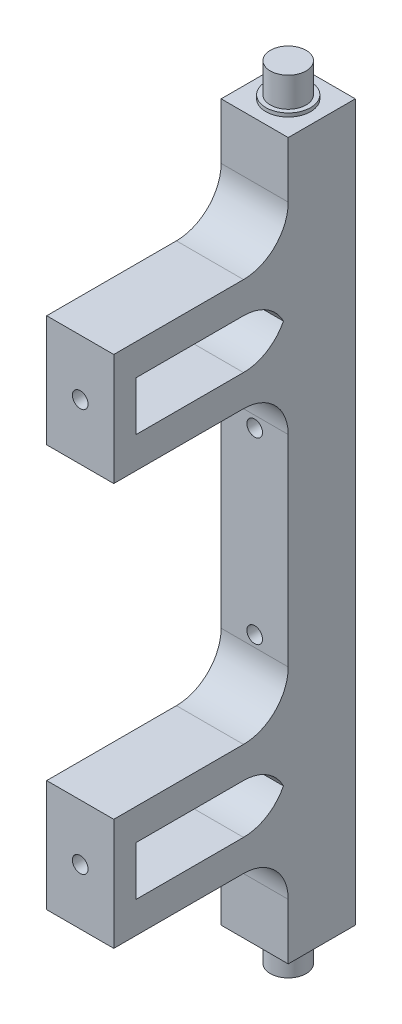
SolidWorks part; units mm, degrees
ref_plane "Plan de face" through (0, 0, 0) normal (1, 0, 0) x (0, 1, 0)
ref_plane "Plan de dessus" through (0, 0, 0) normal (0, 0, 1) x (0, 1, 0)
ref_plane "Plan de droite" through (0, 0, 0) normal (0, 1, 0) x (-1, 0, 0)
sketch "Esquisse1" plane through (0, 0, 0) normal (0, 0, 1) x (0, 1, 0)
  line L0 (0, 0) -> (-102.3211, 0) construction
  line L1 (-57.5, 7.5) -> (-32.5, 7.5)
  line L2 (-57.5, 7.5) -> (-57.5, -7.5)
  line L3 (-57.5, -7.5) -> (-32.5, -7.5)
  line L4 (-32.5, 7.5) -> (-32.5, -7.5)
  line L5 (-57.5, 7.5) -> (-32.5, -7.5) construction
  line L6 (-57.5, -7.5) -> (-32.5, 7.5) construction
  line L7 (0, 0) -> (0, -24.159) construction
  line L8 (57.5, -7.5) -> (32.5, -7.5)
  line L9 (32.5, 7.5) -> (32.5, -7.5)
  line L10 (57.5, 7.5) -> (32.5, 7.5)
  line L11 (57.5, 7.5) -> (57.5, -7.5)
  point P0 (-45, 0)
  dimension "D1" = 45
  dimension "D2" = 25
  dimension "D3" = 15
extrude "Boss.-Extru.1" add sketch "Esquisse1" along normal blind 39
sketch "Esquisse3" plane through (0, 0, 0) normal (0, 0, 1) x (0, 1, 0)
  line L1 (-80, -7.5) -> (80, -7.5)
  line L2 (-80, -7.5) -> (-80, 7.5)
  line L3 (-80, 7.5) -> (80, 7.5)
  line L4 (80, -7.5) -> (80, 7.5)
  line L5 (-80, -7.5) -> (80, 7.5) construction
  line L6 (-80, 7.5) -> (80, -7.5) construction
  point P0 (0, 0)
  dimension "D1" = 160
  dimension "D2" = 15
extrude "Boss.-Extru.2" add sketch "Esquisse3" against normal blind 15
sketch "Esquisse4" plane through (0, -80, 0) normal (0, -1, 0) x (-1, 0, 0)
  line L0 (-7.5, 0) -> (7.5, 15) construction
  line L1 (7.5, 15) -> (7.5, 0) construction
  line L2 (7.5, 0) -> (-7.5, 15) construction
  circle A0 centre (0, 7.5) radius 4
  circle A1 centre (0, 7.5) radius 5
  dimension "D1" = 10
extrude "Boss.-Extru.5" add sketch "Esquisse4" along normal blind 0.8 contours A0 | A1 region at (0, -80, -7.5)
extrude "Boss.-Extru.6" add sketch "Esquisse4<6>" along normal blind 7.4 contours A0 region at (0, -80, -7.5)
sketch "Esquisse4<6>" plane through (0, -80, 0) normal (0, -1, 0) x (-1, 0, 0) same geometry as "Esquisse4"
mirror "Symétrie2" about plane through (0, 0, 0) normal (0, 1, 0) of "Boss.-Extru.5", "Boss.-Extru.6"
fillet "Congé1" radius 10 4 edges at (0, -32.5, 0) (0, -57.5, 0) (0, 57.5, 0) (0, 32.5, 0)
sketch "Esquisse5" plane through (-7.5, 0, 0) normal (-1, 0, 0) x (0, -1, 0)
  line L0 (0, 0) -> (0, 29.4885) construction
  line L2 (32.5, 39) -> (57.5, 39) construction
  line L3 (39.5, 34) -> (50.5, 34)
  line L4 (39.5, 34) -> (39.5, 0)
  line L5 (39.5, 0) -> (50.5, 0)
  line L6 (50.5, 34) -> (50.5, 0)
  line L7 (32.5, 39) -> (32.5, 10) construction
  line L8 (57.5, 39) -> (57.5, 10) construction
  line L9 (-80, -15) -> (80, -15) construction
  line L10 (-50.5, 34) -> (-50.5, 0)
  line L11 (-39.5, 0) -> (-50.5, 0)
  line L12 (-39.5, 34) -> (-39.5, 0)
  line L13 (-39.5, 34) -> (-50.5, 34)
  dimension "D1" = 5
  dimension "D2" = 7
  dimension "D3" = 7
  dimension "D4" = 11
  dimension "D5" = 15
extrude "Enlèv. mat.-Extru.1" cut sketch "Esquisse5" against normal through all
fillet "Congé2" radius 10 4 edges at (0, 39.5, 0) (0, 50.5, 0) (0, -39.5, 0) (0, -50.5, 0)
sketch "Esquisse6" plane through (0, 0, 34) normal (0, 0, -1) x (1, 0, 0)
  line L0 (0, 0) -> (-5.7044, 0) construction
  line L1 (0, 0) -> (0, 13.0401) construction
  line L2 (-7.5, 57.5) -> (7.5, 57.5) construction
  line L3 (7.5, 32.5) -> (-7.5, 32.5) construction
  line L4 (7.5, 32.5) -> (-7.5, 32.5) construction
  circle A0 centre (0, 45) radius 1.75
  circle A1 centre (0, -45) radius 1.75
  dimension "D2" = 12.5
  dimension "D3" = 3.5
  dimension "D4" = 90
  dimension "D1" = 25
extrude "Enlèv. mat.-Extru.2" cut sketch "Esquisse6" against normal through all
sketch "Esquisse7" plane through (0, 0, 0) normal (0, 0, 1) x (1, 0, 0)
  line L9 (-7.5, 22.5) -> (-27.5, 22.5)
  line L10 (-27.5, 22.5) -> (-27.5, -22.5)
  line L11 (-27.5, -22.5) -> (-7.5, -22.5)
  line L12 (-7.5, -22.5) -> (-7.5, -12.5)
  line L13 (-7.5, 22.5) -> (-7.5, -22.5) construction
  line L14 (-7.5, -12.5) -> (-17.5, -12.5)
  line L15 (-17.5, -12.5) -> (-17.5, 12.5)
  line L16 (-17.5, 12.5) -> (-7.5, 12.5)
  line L21 (-7.5, 22.5) -> (-7.5, -22.5)
  line L22 (-7.5, -22.5) -> (7.5, -22.5)
  line L23 (7.5, -22.5) -> (7.5, 22.5)
  line L24 (7.5, 22.5) -> (-7.5, 22.5)
  line L25 (-7.5, 22.5) -> (-7.5, 12.5)
  dimension "D1" = 10
  dimension "D2" = 10
  dimension "D3" = 10
  dimension "D4" = 25
  dimension "D5" = 10
  dimension "D6" = 0
extrude "Boss.-Extru.8" [suppressed] add sketch "Esquisse7" against normal blind 15
sketch "Esquisse8" [suppressed] plane through (0, 0, 0) normal (0, 0, 1) x (1, 0, 0)
  line L0 (-7.5, -12.5) -> (-17.5, -12.5) construction
  line L1 (-7.5, 12.5) -> (36.6313, 12.5)
  line L2 (-7.5, 12.5) -> (-7.5, -12.5)
  line L3 (-7.5, -12.5) -> (36.6313, -12.5)
  line L4 (36.6313, 12.5) -> (36.6313, -12.5)
extrude "Enlèv. mat.-Extru.3" [suppressed] cut sketch "Esquisse8" against normal through all
fillet "Congé3" [suppressed] radius 7
sketch "Esquisse10" [suppressed] plane through (0, 0, 0) normal (0, 0, 1) x (1, 0, 0)
  line L0 (-27.5, 15.5) -> (-27.5, -15.5) construction
  line L4 (-22.5, 0) -> (-22.5, 5.692) construction
  line L7 (-3.5, 17.5) -> (-5.9374, 17.5) construction
  line L8 (-14.5, 22.5) -> (-20.5, 22.5) construction
  line L9 (-10.5, -17.5) -> (-14.5, -17.5) construction
  line L10 (-10.5, 12.5) -> (0.5, 12.5) construction
  line L11 (-17.5, -5.5) -> (-17.5, 5.5) construction
  circle A0 centre (-22.5, 17.5) radius 1.75
  circle A1 centre (-22.5, -17.5) radius 1.75
  dimension "D1" = 3.5
  dimension "D2" = 3.5
  dimension "D3" = 5
  dimension "D4" = 5
  dimension "D5" = 5
  dimension "D6" = 5
extrude "Enlèv. mat.-Extru.4" [suppressed] cut sketch "Esquisse10" against normal through all
ref_plane "Plan1" through (7.5, 32.5, 39) normal (0, 0, -1) x (-1, 0, 0)
sketch "Esquisse11" plane through (0, 0, 0) normal (0, 0, 1) x (0, 1, 0)
  circle A0 centre (20, 0) radius 1.75
  circle A1 centre (-20, 0) radius 1.75
extrude "Trous vis support capteurs" cut sketch "Esquisse11" against normal through all
